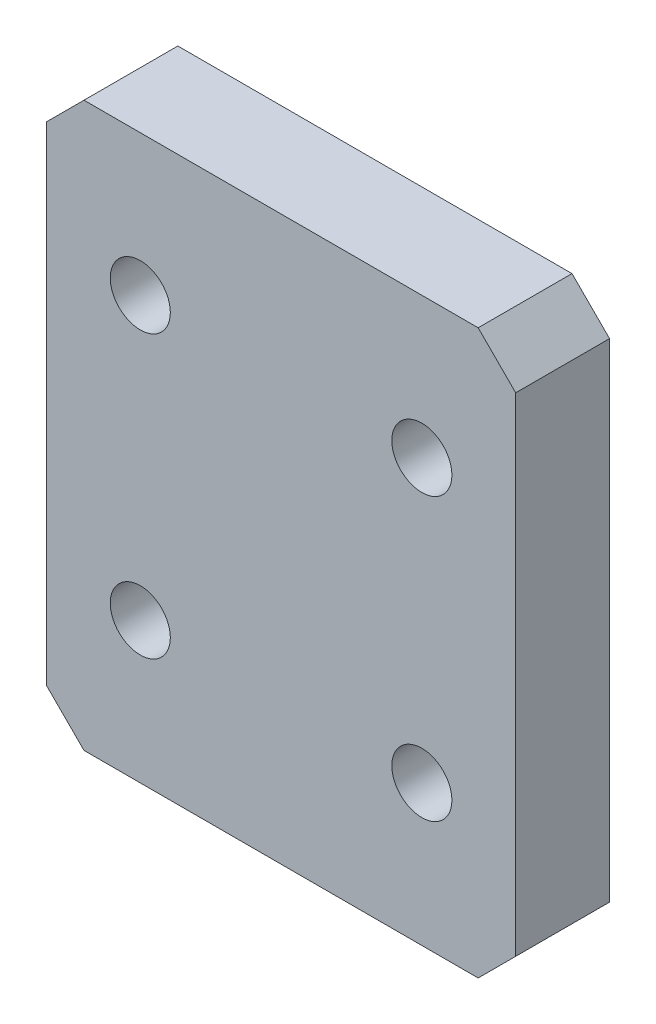
SolidWorks part; units mm, degrees
material "鑄碳鋼"
ref_plane "前基準面" through (0, 0, 0) normal (0, 0, 1) x (1, 0, 0)
ref_plane "上基準面" through (0, 0, 0) normal (0, 1, 0) x (1, 0, 0)
ref_plane "右基準面" through (0, 0, 0) normal (1, 0, 0) x (0, 0, -1)
sketch "草圖1" plane through (0, 0, 0) normal (0, 0, 1) x (1, 0, 0)
  line L1 (-12.5, -15) -> (12.5, -15)
  line L2 (-12.5, -15) -> (-12.5, 15)
  line L3 (-12.5, 15) -> (12.5, 15)
  line L4 (12.5, -15) -> (12.5, 15)
  line L5 (-12.5, -15) -> (12.5, 15) construction
  line L6 (-12.5, 15) -> (12.5, -15) construction
  point P0 (0, 0)
  dimension "D1" = 25
  dimension "D2" = 30
extrude "填料-伸長1" add sketch "草圖1" along normal blind 5
sketch "草圖4" plane through (0, 0, 5) normal (0, 0, 1) x (1, 0, 0)
  line L0 (0, 0) -> (-7.5, 0) construction
  line L1 (-7.5, 0) -> (-7.5, 7.5) construction
  circle A0 centre (-7.5, 7.5) radius 1.6
  dimension "D3" = 3.2
  dimension "D1" = 7.5
  dimension "D2" = 7.5
extrude "除料-伸長3" cut sketch "草圖4" against normal through all
pattern_linear "直線複製排列1" count 2 spacing 15 along (1, 0, 0) count 2 spacing 15 along (0, -1, 0) of "除料-伸長3"
chamfer "導角1" distance 2 angle 45 4 edges at (12.5, -15, 2.5) (-12.5, -15, 2.5) (-12.5, 15, 2.5) (12.5, 15, 2.5)
